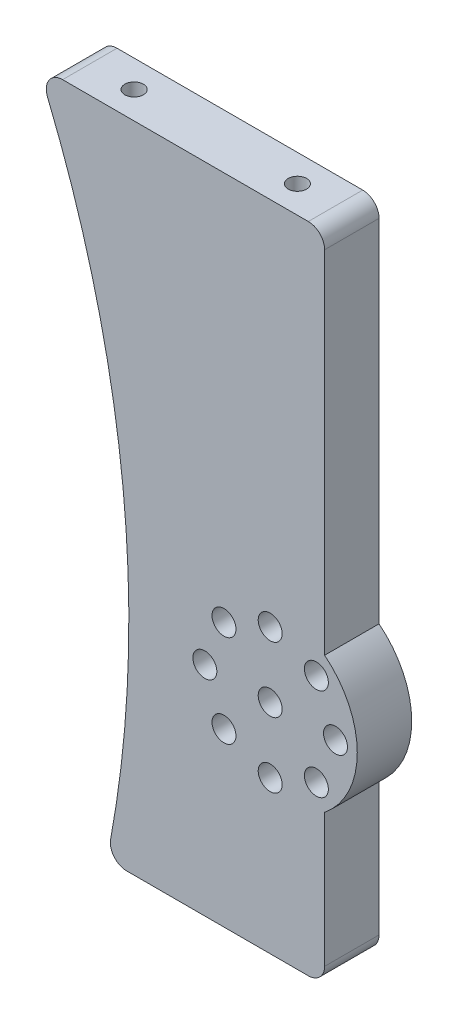
SolidWorks part; units mm, degrees
material "ABS"
ref_plane "正面" through (0, 0, 0) normal (0, 0, 1) x (1, 0, 0)
ref_plane "平面" through (0, 0, 0) normal (0, 1, 0) x (1, 0, 0)
ref_plane "右側面" through (0, 0, 0) normal (1, 0, 0) x (0, 0, -1)
sketch "ｽｹｯﾁ1" plane through (0, 0, 0) normal (0, 0, 1) x (1, 0, 0)
  line L0 (0, 0) -> (0, 60) construction
  line L1 (-5, 60) -> (5, 60)
  line L2 (-5, 60) -> (-5, 26.245)
  line L3 (-5, 0) -> (5, 0)
  line L4 (5, 60) -> (5, 26.245)
  line L5 (5, 13.755) -> (5, 0)
  line L7 (-5, 13.755) -> (-5, 0)
  circle A0 centre (0, 20) radius 1.1
  circle A1 centre (0, 20) radius 6 construction
  circle A2 centre (0, 26) radius 1.1
  circle A4 centre (4.2426, 24.2426) radius 1.1
  circle A5 centre (6, 20) radius 1.1
  circle A6 centre (4.2426, 15.7574) radius 1.1
  circle A7 centre (0, 14) radius 1.1
  circle A8 centre (-4.2426, 15.7574) radius 1.1
  circle A9 centre (-6, 20) radius 1.1
  circle A10 centre (-4.2426, 24.2426) radius 1.1
  arc A11 (-5, 26.245) -> (-5, 13.755) centre (0, 20) ccw
  arc A12 (5, 13.755) -> (5, 26.245) centre (0, 20) ccw
  point P29 (0, 20)
  dimension "D3" = 2.2
  dimension "D5" = 12
  dimension "D6" = 2.2
  dimension "D8" = 16
  dimension "D1" = 10
  dimension "D2" = 60
  dimension "D4" = 20
  dimension "D7" = 8
extrude "ﾎﾞｽ - 押し出し1" add sketch "ｽｹｯﾁ1" along normal blind 5
sketch "ｽｹｯﾁ2" plane through (0, 0, 0) normal (0, 0, -1) x (-1, 0, 0)
  line L0 (5, 60) -> (21.3281, 60)
  line L2 (0, 20) -> (112.9796, 20) construction
  line L5 (5, 0) -> (15, 0)
  line L6 (5, 13.755) -> (5, 0) construction
  line L7 (5, 60) -> (5, 26.245) construction
  line L8 (5, 13.755) -> (5, 0)
  line L9 (5, 60) -> (5, 26.245)
  arc A0 (21.3281, 60) -> (15, 0) centre (112.9796, 20) ccw
  arc A1 (5, 13.755) -> (5, 26.245) centre (0, 20) ccw construction
  arc A2 (5, 13.755) -> (5, 26.245) centre (0, 20) ccw
  dimension "D1" = 10
  dimension "D2" = 200
extrude "ﾎﾞｽ - 押し出し2" add sketch "ｽｹｯﾁ2" against normal blind 5
fillet "ﾌｨﾚｯﾄ1" radius 1.5 4 edges at (-15, 0, 2.5) (-21.3281, 60, 2.5) (5, 60, 2.5) (5, 0, 2.5)
sketch "ｽｹｯﾁ3" plane through (0, 0, 0) normal (0, -1, 0) x (1, 0, 0)
  line L0 (5, 2.5) -> (-14.4472, 2.5) construction
  line L2 (-13.1798, 0) -> (3.5, 0) construction
  line L3 (5, 5) -> (5, 0) construction
  circle A0 centre (0, 2.5) radius 0.85
  circle A1 centre (-10, 2.5) radius 0.85
  point P8 (0, 0)
  point P9 (0, 0)
  point P10 (0.2386, 2.5)
  point P11 (0, 0)
  dimension "D1" = 1.7
  dimension "D2" = 5
  dimension "D3" = 10
  dimension "D4" = 2.5
extrude "ｶｯﾄ - 押し出し1" cut sketch "ｽｹｯﾁ3" against normal blind 10
sketch "ｽｹｯﾁ4" plane through (0, 60, 0) normal (0, 1, 0) x (1, 0, 0)
  line L0 (5, -2.5) -> (-23.5343, -2.5) construction
  line L1 (5, 0) -> (5, -5) construction
  circle A0 centre (0, -2.5) radius 0.85
  circle A1 centre (-15, -2.5) radius 0.85
  dimension "D1" = 1.7
  dimension "D2" = 5
  dimension "D3" = 15
extrude "ｶｯﾄ - 押し出し2" cut sketch "ｽｹｯﾁ4" against normal blind 10
